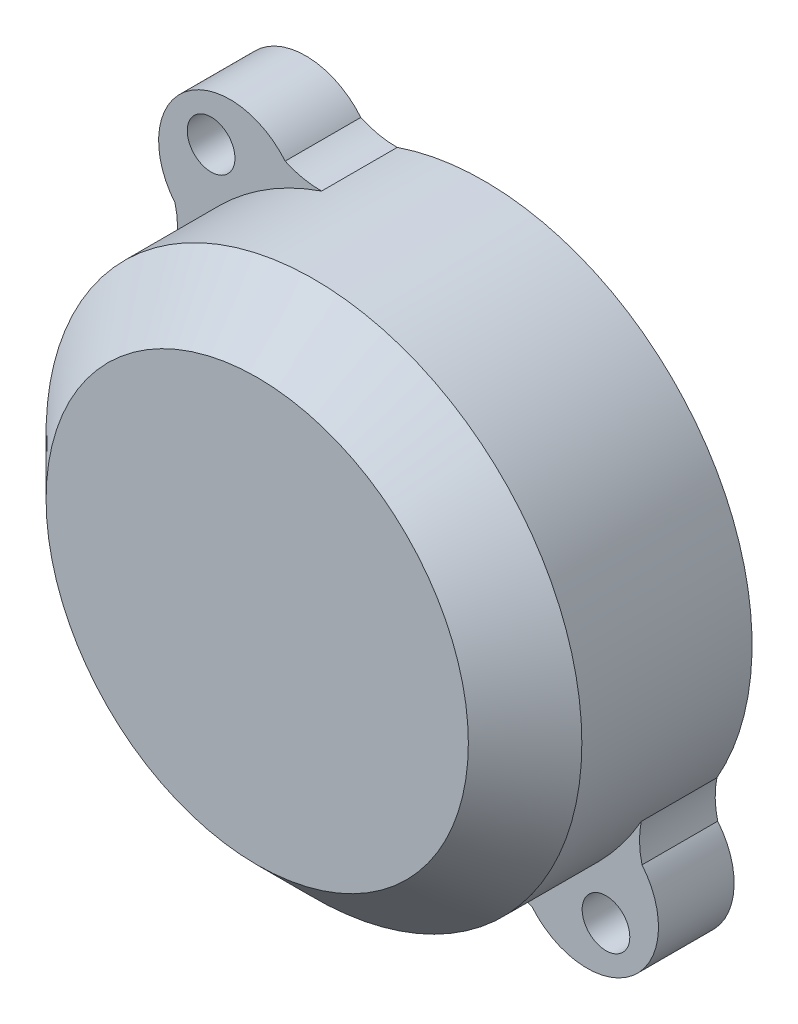
SolidWorks part; units mm, degrees
material "ABS"
ref_plane "X-Y Datum" through (0, 0, 0) normal (0, 0, 1) x (1, 0, 0)
ref_plane "X-Z Datum" through (0, 0, 0) normal (0, 1, 0) x (1, 0, 0)
ref_plane "Y-Z Datum" through (0, 0, 0) normal (1, 0, 0) x (0, 0, -1)
sketch "Sketch1" plane through (0, 0, -959.8494) normal (0, 0, 1) x (1, 0, 0)
  line L0 (-187.0313, 1325.7896) -> (-148.1313, 1325.7896) construction
  line L1 (-153.2432, 1308.4731) -> (-181.9194, 1343.106) construction
  line L3 (-186.5408, 1339.2795) -> (-177.298, 1346.9326) construction
  line L4 (-186.5408, 1339.2795) -> (-187.1786, 1340.0497) construction
  line L5 (-177.298, 1346.9326) -> (-177.9358, 1347.7028) construction
  line L6 (-181.9194, 1343.106) -> (-186.3837, 1348.4977) construction
  line L7 (-184.8978, 1311.4515) -> (-150.2649, 1340.1277) construction
  circle A0 centre (-167.5813, 1325.7896) radius 19.45 construction
  circle A1 centre (-167.5813, 1325.7896) radius 22.482
  circle A2 centre (-167.5813, 1325.7896) radius 20.45 construction
  arc A3 (-187.1786, 1340.0497) -> (-177.9358, 1347.7028) centre (-182.5572, 1343.8763) cw
  circle A4 centre (-184.1516, 1345.8019) radius 2
  arc A5 (-187.1786, 1340.0497) -> (-187.1117, 1336.9254) centre (-193.9624, 1338.3415) cw
  arc A6 (-177.9358, 1347.7028) -> (-174.8788, 1347.0543) centre (-174.9922, 1354.049) ccw
  arc A7 (-147.9841, 1311.5295) -> (-148.051, 1314.6538) centre (-141.2002, 1313.2377) cw
  circle A8 centre (-151.0111, 1305.7773) radius 2
  arc A9 (-157.2269, 1303.8764) -> (-147.9841, 1311.5295) centre (-152.6055, 1307.7029) ccw
  arc A10 (-157.2269, 1303.8764) -> (-160.2839, 1304.5249) centre (-160.1705, 1297.5302) ccw
  point P11 (-167.5813, 1325.7896)
  point P14 (-181.9194, 1343.106)
  point P15 (-181.9194, 1343.106)
  point P27 (-167.5813, 1325.7896)
  point P29 (-167.5813, 1325.7896)
  circle M7 centre (-168.7041, 1313.6916) radius 2.8
  circle M8 centre (-167.5813, 1325.7896) radius 19.45
  line M9 (-167.9662, 1333.709) -> (-165.7457, 1333.503)
  line M10 (-165.7457, 1333.503) -> (-167.1965, 1317.8701)
  line M11 (-167.1965, 1317.8701) -> (-169.417, 1318.0762)
  line M12 (-169.417, 1318.0762) -> (-167.9662, 1333.709)
  circle M13 centre (-176.4432, 1326.612) radius 5
  circle M14 centre (-158.7194, 1324.9672) radius 5
  dimension "D1" = 40.9
  dimension "D2" = 2.032
  dimension "D4" = 1
  dimension "D5" = 4
  dimension "D6" = 1.9256
  dimension "D7" = 12.3146
  dimension "D8" = 6.9956
  dimension "D3" = 12
extrude "Boss-Extrude1" add sketch "Sketch1" along normal blind 19.05 contours M8 M14 M13 M12 M9 M10 M11 M7 | M13 | M9 M12 M11 M10 | M14 | M7 | A1 M8 region at (-146.4644, 1320.1923, -959.8494) region at (-168.7041, 1313.6916, -959.8494) region at (-186.4812, 1325.7896, -959.8494) region at (-167.5813, 1325.7896, -959.8494) region at (-176.4432, 1326.612, -959.8494) region at (-158.7194, 1324.9672, -959.8494)
extrude "Boss-Extrude3" add sketch "Sketch1<5>" along normal blind 6.35 contours A6 A3 A5 A1 A4 | A10 A9 A7 A1 A8 region at (-182.0396, 1343.2511, -959.8494) region at (-148.3825, 1313.0838, -959.8494)
sketch "Sketch1<5>" plane through (0, 0, -959.8494) normal (0, 0, 1) x (1, 0, 0) same geometry as "Sketch1"
chamfer "Chamfer1" distance 4.7625 angle 45 1 edges at (-145.0993, 1325.7896, -940.7994)
shell "Shell1" thickness 2 removed face at (-167.5813, 1325.7896, -959.8494)
ref_plane "Plane1" through (-302.8065, 26.2507, 0) normal (-0.9963, 0.0864, 0) x (0, 0, 1)
